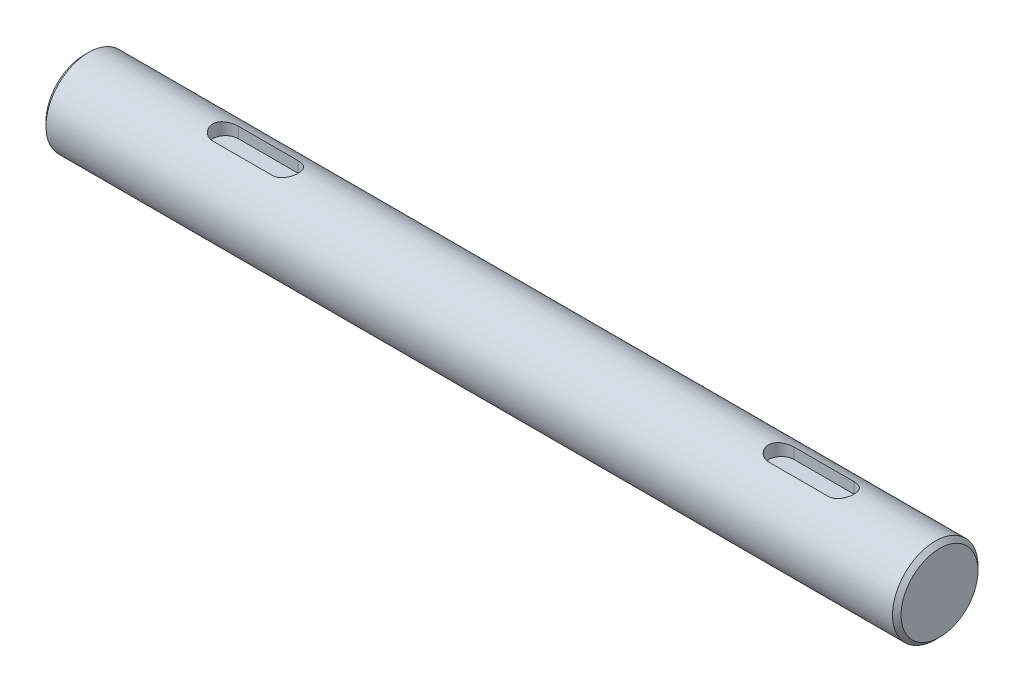
SolidWorks part; units mm, degrees
material "45"
ref_plane "前视基准面" through (0, 0, 0) normal (0, 0, 1) x (1, 0, 0)
ref_plane "上视基准面" through (0, 0, 0) normal (0, 1, 0) x (1, 0, 0)
ref_plane "右视基准面" through (0, 0, 0) normal (1, 0, 0) x (0, 0, -1)
ref_axis "基准轴1" through (88.99, 0, 0) along (-1, 0, 0)
sketch "草图1" plane through (0, 0, 0) normal (1, 0, 0) x (0, 0, -1)
  circle A0 centre (0, 0) radius 10
extrude "凸台-拉伸1" add sketch "草图1" along normal blind 200
ref_plane "基准面1" through (0, 10, 0) normal (0, 1, 0) x (1, 0, 0)
sketch "草图2" plane through (0, 10, 0) normal (0, 1, 0) x (1, 0, 0)
  line L0 (33, 3) -> (47, 3)
  line L1 (33, -3) -> (47, -3)
  arc A0 (33, 3) -> (33, -3) centre (33, 0) ccw
  arc A1 (47, 3) -> (47, -3) centre (47, 0) cw
  dimension "D1" = 3
  dimension "D2" = 14
extrude "切除-拉伸1" cut sketch "草图2" against normal blind 3
chamfer "倒角1" distance 1 angle 45 1 edges at (0, 0, -10)
pattern_linear "阵列(线性)1" count 3 spacing 130 along (1, 0, 0) of "切除-拉伸1"
chamfer "倒角2" distance 1 angle 45 1 edges at (200, 0, -10)
sketch "草图4" plane through (0, 0, 0) normal (-1, 0, 0) x (0, 0, 1)
  circle A0 centre (0, 0) radius 10
  circle A1 centre (0, 0) radius 5
  dimension "D1" = 10
